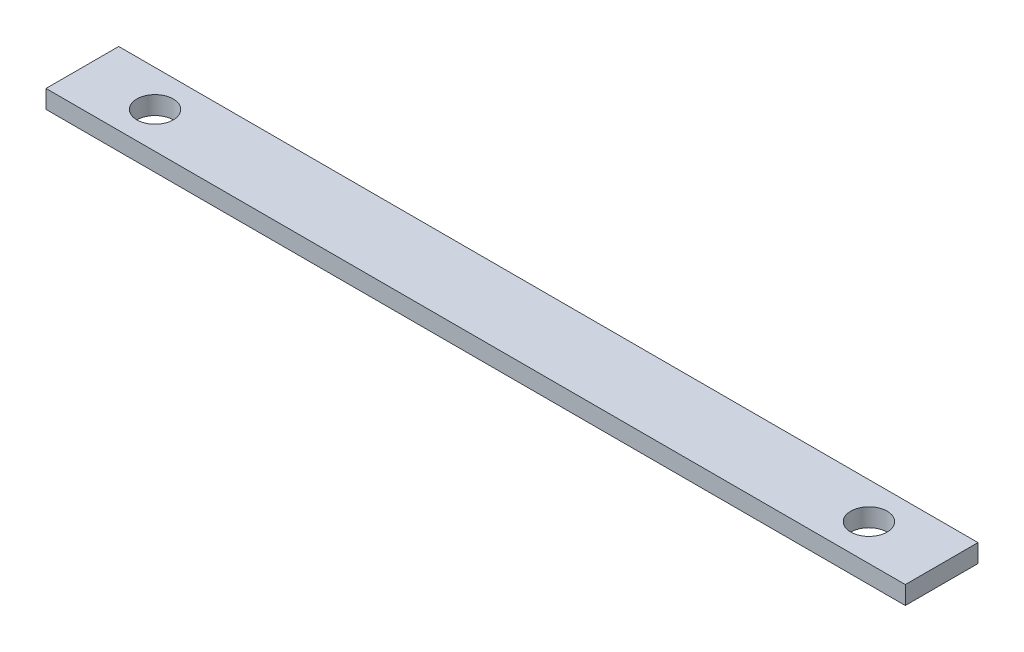
SolidWorks part; units mm, degrees
ref_plane "Front Plane" through (0, 0, 0) normal (0, 0, 1) x (1, 0, 0)
ref_plane "Top Plane" through (0, 0, 0) normal (0, 1, 0) x (1, 0, 0)
ref_plane "Right Plane" through (0, 0, 0) normal (1, 0, 0) x (0, 0, -1)
sketch "Sketch1" plane through (0, 0, 0) normal (0, 1, 0) x (1, 0, 0)
  line L1 (0, 0) -> (150.114, 0)
  line L2 (0, 0) -> (0, 12.7)
  line L3 (0, 12.7) -> (150.114, 12.7)
  line L4 (150.114, 0) -> (150.114, 12.7)
  dimension "D1" = 150.114
  dimension "D2" = 12.7
extrude "Boss-Extrude1" add sketch "Sketch1" along normal blind 3.175
sketch "Sketch2" plane through (0, 3.175, 0) normal (0, 1, 0) x (1, 0, 0)
  line L0 (0, 12.7) -> (0, 0) construction
  line L1 (150.114, 0) -> (150.114, 12.7) construction
  circle A0 centre (12.7, 6.35) radius 3.175
  circle A1 centre (137.414, 6.35) radius 3.175
  point P4 (0, 0)
  point P5 (0, 0)
  point P8 (0, 6.35)
  point P9 (15.3333, 6.35)
  point P12 (207.264, 6.35)
  dimension "D1" = 6.35
  dimension "D2" = 12.7
  dimension "D3" = 12.7
  dimension "D4" = 6.35
extrude "Cut-Extrude1" cut sketch "Sketch2" against normal through all
